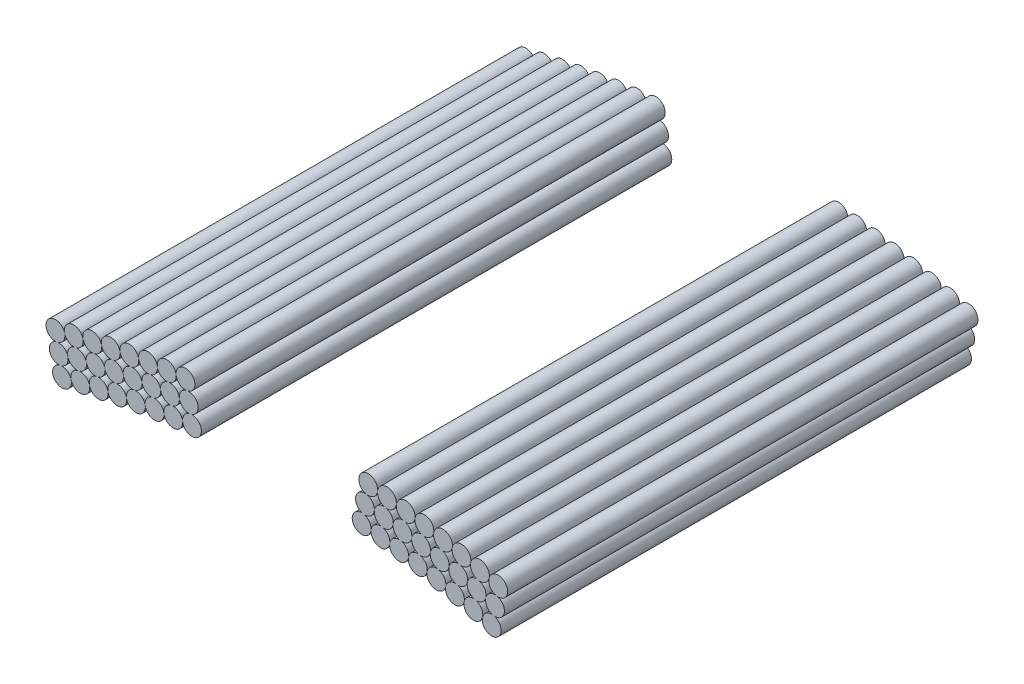
SolidWorks part; units mm, degrees
material "Copper"
ref_plane "Front Plane" through (0, 0, 0) normal (0, 0, 1) x (1, 0, 0)
ref_plane "Top Plane" through (0, 0, 0) normal (0, 1, 0) x (1, 0, 0)
ref_plane "Right Plane" through (0, 0, 0) normal (1, 0, 0) x (0, 0, -1)
sketch "Sketch1" plane through (0, 0, 0) normal (0, 0, 1) x (1, 0, 0)
  line L0 (0, 0) -> (-4.2725, 48.8355) construction
  line L1 (0, 0) -> (4.2725, 48.8355) construction
  line L2 (0, 0) -> (50000, 0) construction
  line L3 (0, 0) -> (0, -50000) construction
  line L4 (0, 0) -> (-12940.9523, 48296.2913) construction
  line L5 (0, 0) -> (-8682.4089, 49240.3877) construction
  circle A0 centre (0, 0) radius 46.228 construction
  arc A1 (4.2725, 48.8355) -> (-4.2725, 48.8355) centre (0, 0) ccw construction
  circle A2 centre (-10.613, 45.5169) radius 0.5098
  circle A3 centre (-9.6176, 45.7376) radius 0.5098
  circle A4 centre (-8.6175, 45.9365) radius 0.5098
  circle A5 centre (-7.6134, 46.1136) radius 0.5098
  circle A6 centre (-6.6056, 46.2687) radius 0.5098
  circle A7 centre (-4.5811, 46.5128) radius 0.5098
  circle A8 centre (-5.5947, 46.4018) radius 0.5098
  circle A9 centre (-11.6035, 45.2745) radius 0.5098
  dimension "D1" = 92.456
  dimension "D3" = 98.044
  dimension "D5" = 5
  dimension "D2" = 10
  dimension "D4" = 15
extrude "Boss-Extrude1" add sketch "Sketch1" against normal blind 25.4 contours A9 | A2 | A3 | A4 | A5 | A6 | A8 | A7 region at (-11.6035, 45.2745, 0)
ref_axis "Axis5" through (0, 0, 0) along (-1, 0, 0)
ref_axis "Axis6" through (0, 0, 0) along (0, 1, 0)
ref_axis "Axis7" through (0, 0, 0) along (0, 0, 1)
ref_plane "Plane1" through (0, 0, 0) normal (-0.1736, 0.9848, 0) x (0, 0, 1)
ref_axis "Axis9" through (0, 0, 0) along (-0.1736, 0.9848, 0)
pattern_linear "LPattern1" count 3 spacing 1.016 along (-0.1736, 0.9848, 0) of "Boss-Extrude1"
mirror "Mirror1" about plane through (0, 0, 0) normal (1, 0, 0) of bodies 116 115 114 113 112 111 110 109
